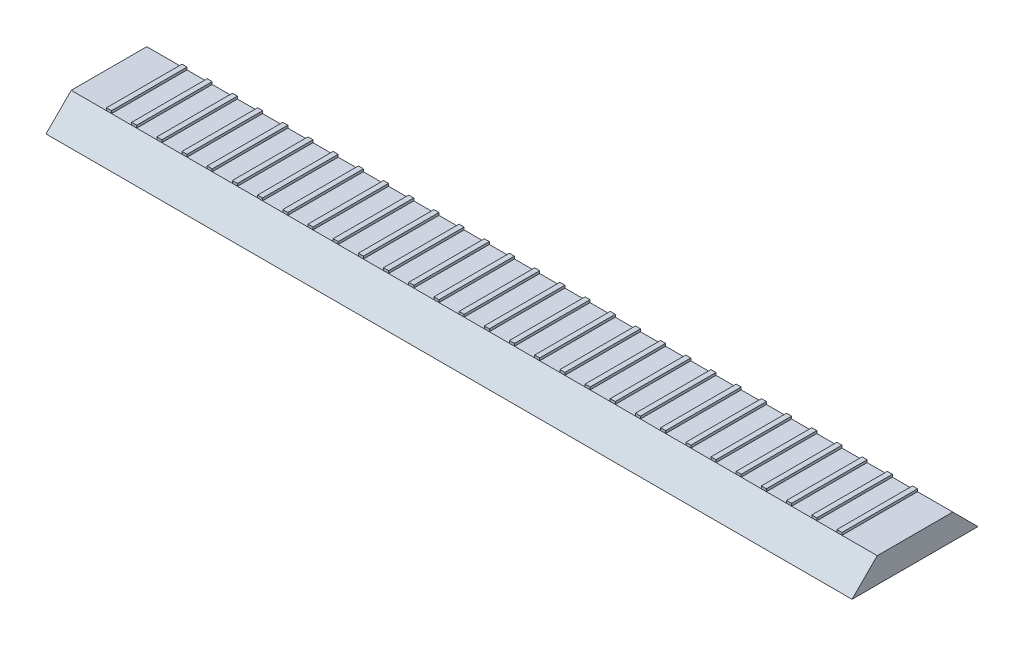
SolidWorks part; units mm, degrees
ref_plane "Front Plane" through (0, 0, 0) normal (0, 0, 1) x (1, 0, 0)
ref_plane "Top Plane" through (0, 0, 0) normal (0, 1, 0) x (1, 0, 0)
ref_plane "Right Plane" through (0, 0, 0) normal (1, 0, 0) x (0, 0, -1)
sketch "Sketch1" plane through (0, 0, 0) normal (0, 1, 0) x (1, 0, 0)
  line L1 (-80, -17.5) -> (80, -17.5)
  line L2 (-80, -17.5) -> (-80, 17.5)
  line L3 (-80, 17.5) -> (80, 17.5)
  line L4 (80, -17.5) -> (80, 17.5)
  line L5 (-80, -17.5) -> (80, 17.5) construction
  line L6 (-80, 17.5) -> (80, -17.5) construction
  point P0 (0, 0)
  dimension "D1" = 35
  dimension "D2" = 160
extrude "Boss-Extrude1" add sketch "Sketch1" along normal blind 5
chamfer "Chamfer1" distance 10 angle 45 2 edges at (0, 5, -17.5) (0, 5, 17.5)
sketch "Sketch2" plane through (0, 5, 0) normal (0, 1, 0) x (1, 0, 0)
  line L0 (80, 0) -> (-80, 0) construction
  line L1 (80, -7.5) -> (80, 7.5) construction
  line L2 (-80, 7.5) -> (-80, -7.5) construction
  line L3 (-80, -7.5) -> (80, -7.5) construction
  line L4 (73, 7.5) -> (72, 7.5)
  line L5 (73, 7.5) -> (73, -7.5)
  line L6 (73, -7.5) -> (72, -7.5)
  line L7 (72, 7.5) -> (72, -7.5)
  line L8 (73, 7.5) -> (72, -7.5) construction
  line L9 (73, -7.5) -> (72, 7.5) construction
  line L10 (67, 7.5) -> (67, -7.5)
  line L11 (68, 7.5) -> (68, -7.5)
  line L12 (68, 7.5) -> (67, 7.5)
  line L13 (68, -7.5) -> (67, -7.5)
  line L14 (62, 7.5) -> (62, -7.5)
  line L15 (63, 7.5) -> (63, -7.5)
  line L16 (63, 7.5) -> (62, 7.5)
  line L17 (63, -7.5) -> (62, -7.5)
  line L18 (57, 7.5) -> (57, -7.5)
  line L19 (58, 7.5) -> (58, -7.5)
  line L20 (58, 7.5) -> (57, 7.5)
  line L21 (58, -7.5) -> (57, -7.5)
  line L22 (52, 7.5) -> (52, -7.5)
  line L23 (53, 7.5) -> (53, -7.5)
  line L24 (53, 7.5) -> (52, 7.5)
  line L25 (53, -7.5) -> (52, -7.5)
  line L26 (47, 7.5) -> (47, -7.5)
  line L27 (48, 7.5) -> (48, -7.5)
  line L28 (48, 7.5) -> (47, 7.5)
  line L29 (48, -7.5) -> (47, -7.5)
  line L30 (42, 7.5) -> (42, -7.5)
  line L31 (43, 7.5) -> (43, -7.5)
  line L32 (43, 7.5) -> (42, 7.5)
  line L33 (43, -7.5) -> (42, -7.5)
  line L34 (37, 7.5) -> (37, -7.5)
  line L35 (38, 7.5) -> (38, -7.5)
  line L36 (38, 7.5) -> (37, 7.5)
  line L37 (38, -7.5) -> (37, -7.5)
  line L38 (32, 7.5) -> (32, -7.5)
  line L39 (33, 7.5) -> (33, -7.5)
  line L40 (33, 7.5) -> (32, 7.5)
  line L41 (33, -7.5) -> (32, -7.5)
  line L42 (27, 7.5) -> (27, -7.5)
  line L43 (28, 7.5) -> (28, -7.5)
  line L44 (28, 7.5) -> (27, 7.5)
  line L45 (28, -7.5) -> (27, -7.5)
  line L46 (22, 7.5) -> (22, -7.5)
  line L47 (23, 7.5) -> (23, -7.5)
  line L48 (23, 7.5) -> (22, 7.5)
  line L49 (23, -7.5) -> (22, -7.5)
  line L50 (17, 7.5) -> (17, -7.5)
  line L51 (18, 7.5) -> (18, -7.5)
  line L52 (18, 7.5) -> (17, 7.5)
  line L53 (18, -7.5) -> (17, -7.5)
  line L54 (12, 7.5) -> (12, -7.5)
  line L55 (13, 7.5) -> (13, -7.5)
  line L56 (13, 7.5) -> (12, 7.5)
  line L57 (13, -7.5) -> (12, -7.5)
  line L58 (7, 7.5) -> (7, -7.5)
  line L59 (8, 7.5) -> (8, -7.5)
  line L60 (8, 7.5) -> (7, 7.5)
  line L61 (8, -7.5) -> (7, -7.5)
  line L62 (2, 7.5) -> (2, -7.5)
  line L63 (3, 7.5) -> (3, -7.5)
  line L64 (3, 7.5) -> (2, 7.5)
  line L65 (3, -7.5) -> (2, -7.5)
  line L66 (-3, 7.5) -> (-3, -7.5)
  line L67 (-2, 7.5) -> (-2, -7.5)
  line L68 (-2, 7.5) -> (-3, 7.5)
  line L69 (-2, -7.5) -> (-3, -7.5)
  line L70 (-8, 7.5) -> (-8, -7.5)
  line L71 (-7, 7.5) -> (-7, -7.5)
  line L72 (-7, 7.5) -> (-8, 7.5)
  line L73 (-7, -7.5) -> (-8, -7.5)
  line L74 (-13, 7.5) -> (-13, -7.5)
  line L75 (-12, 7.5) -> (-12, -7.5)
  line L76 (-12, 7.5) -> (-13, 7.5)
  line L77 (-12, -7.5) -> (-13, -7.5)
  line L78 (-18, 7.5) -> (-18, -7.5)
  line L79 (-17, 7.5) -> (-17, -7.5)
  line L80 (-17, 7.5) -> (-18, 7.5)
  line L81 (-17, -7.5) -> (-18, -7.5)
  line L82 (-23, 7.5) -> (-23, -7.5)
  line L83 (-22, 7.5) -> (-22, -7.5)
  line L84 (-22, 7.5) -> (-23, 7.5)
  line L85 (-22, -7.5) -> (-23, -7.5)
  line L86 (-28, 7.5) -> (-28, -7.5)
  line L87 (-27, 7.5) -> (-27, -7.5)
  line L88 (-27, 7.5) -> (-28, 7.5)
  line L89 (-27, -7.5) -> (-28, -7.5)
  line L90 (-33, 7.5) -> (-33, -7.5)
  line L91 (-32, 7.5) -> (-32, -7.5)
  line L92 (-32, 7.5) -> (-33, 7.5)
  line L93 (-32, -7.5) -> (-33, -7.5)
  line L94 (-38, 7.5) -> (-38, -7.5)
  line L95 (-37, 7.5) -> (-37, -7.5)
  line L96 (-37, 7.5) -> (-38, 7.5)
  line L97 (-37, -7.5) -> (-38, -7.5)
  line L98 (-43, 7.5) -> (-43, -7.5)
  line L99 (-42, 7.5) -> (-42, -7.5)
  line L100 (-42, 7.5) -> (-43, 7.5)
  line L101 (-42, -7.5) -> (-43, -7.5)
  line L102 (-48, 7.5) -> (-48, -7.5)
  line L103 (-47, 7.5) -> (-47, -7.5)
  line L104 (-47, 7.5) -> (-48, 7.5)
  line L105 (-47, -7.5) -> (-48, -7.5)
  line L106 (-53, 7.5) -> (-53, -7.5)
  line L107 (-52, 7.5) -> (-52, -7.5)
  line L108 (-52, 7.5) -> (-53, 7.5)
  line L109 (-52, -7.5) -> (-53, -7.5)
  line L110 (-58, 7.5) -> (-58, -7.5)
  line L111 (-57, 7.5) -> (-57, -7.5)
  line L112 (-57, 7.5) -> (-58, 7.5)
  line L113 (-57, -7.5) -> (-58, -7.5)
  line L114 (-63, 7.5) -> (-63, -7.5)
  line L115 (-62, 7.5) -> (-62, -7.5)
  line L116 (-62, 7.5) -> (-63, 7.5)
  line L117 (-62, -7.5) -> (-63, -7.5)
  line L118 (-68, 7.5) -> (-68, -7.5)
  line L119 (-67, 7.5) -> (-67, -7.5)
  line L120 (-67, 7.5) -> (-68, 7.5)
  line L121 (-67, -7.5) -> (-68, -7.5)
  line L122 (-73, 7.5) -> (-73, -7.5)
  line L123 (-72, 7.5) -> (-72, -7.5)
  line L124 (-72, 7.5) -> (-73, 7.5)
  line L125 (-72, -7.5) -> (-73, -7.5)
  point P6 (72.5, 0)
  dimension "D1" = 1
  dimension "D3" = 7
  dimension "D2" = 30
extrude "Boss-Extrude2" add sketch "Sketch2" along normal blind 0.5
